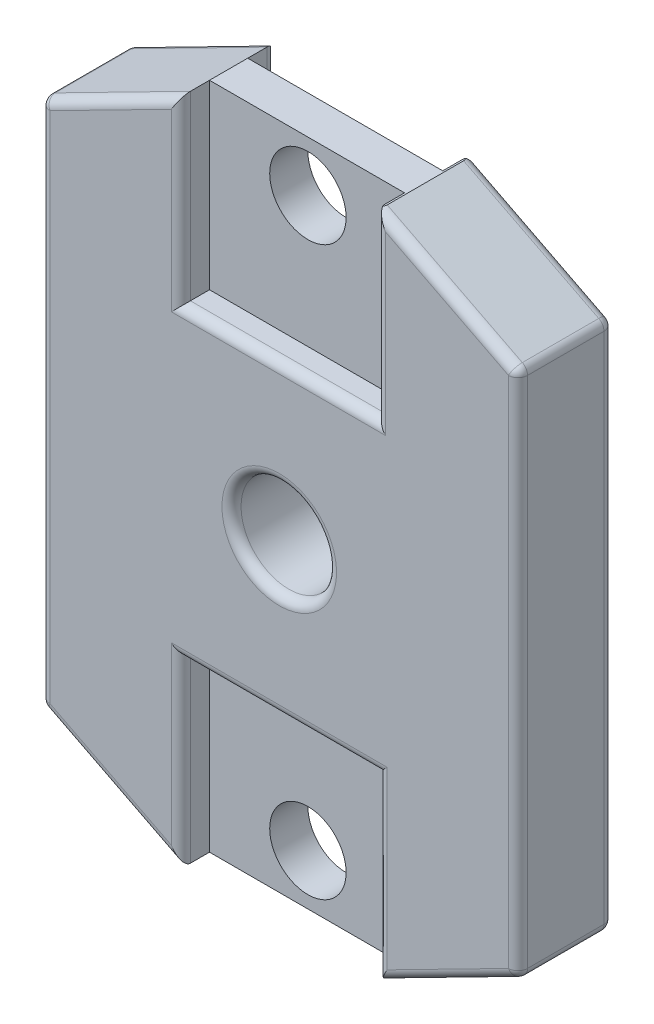
SolidWorks part; units mm, degrees
material "PC 高粘度"
ref_plane "前视基准面" through (0, 0, 0) normal (0, 0, 1) x (1, 0, 0)
ref_plane "上视基准面" through (0, 0, 0) normal (0, 1, 0) x (1, 0, 0)
ref_plane "右视基准面" through (0, 0, 0) normal (1, 0, 0) x (0, 0, -1)
sketch "草图1" plane through (0, 0, 0) normal (0, 0, 1) x (1, 0, 0)
  line L0 (0, 0) -> (5, 0)
  line L1 (0, 0) -> (0, 7)
  line L2 (0, 7) -> (5, 7)
  line L3 (5, 7) -> (5, 0)
  dimension "D1" = 5
extrude "凸台-拉伸1" add sketch "草图1" along normal blind 1
sketch "草图2" plane through (0, 0, 0) normal (0, 0, 1) x (1, 0, 0)
  line L0 (0, 7) -> (5, 0)
  line L1 (0, 0) -> (5, 0) construction
  line L2 (5, 0) -> (5, 7)
  line L3 (5, 7) -> (0, 0)
  circle A0 centre (2.5, 3.5) radius 0.9954
  circle A1 centre (2.5, 3.5) radius 0.7
  circle A2 centre (2.5, 3.5) radius 0.5
extrude "凸台-拉伸2" add sketch "草图2" against normal blind 0.25 contours A1 L3 A0 L0 | A1 L0 A0 L3 | A1 L3 A0 L0 | A1 L0 A0 L3 region at (2.5, 4.3024, 0) region at (1.767, 3.5, 0) region at (3.233, 3.5, 0) region at (2.5, 2.6976, 0)
sketch "草图4" plane through (0, 0, 0) normal (0, 0, -1) x (-1, 0, 0)
  circle A0 centre (-2.5, 3.5) radius 0.7
extrude "凸台-拉伸3" add sketch "草图4" along normal blind 0.35
sketch "草图5" plane through (0, 0, -0.35) normal (0, 0, -1) x (-1, 0, 0)
  circle A0 centre (-2.5, 3.5) radius 0.5
extrude "切除-拉伸1" cut sketch "草图5" against normal through all
sketch "草图7" plane through (0, 0, 0) normal (0, 0, 1) x (1, 0, 0)
  line L0 (3.5303, 0) -> (5, 0)
  line L1 (5, 0) -> (5, 7) construction
  line L2 (0, 0.75) -> (0, 0)
  line L3 (5, 6.25) -> (3.5303, 7)
  line L4 (5, 7) -> (0, 7) construction
  line L6 (5, 0.75) -> (3.5303, 0)
  line L7 (0, 0) -> (5, 0) construction
  line L9 (0, 7) -> (0, 0) construction
  line L11 (0, 0.75) -> (1.4697, 0)
  line L13 (1.4697, 7) -> (0, 6.25)
  line L14 (5, 6.25) -> (5, 7)
  line L15 (5, 7) -> (0, 7)
  line L16 (0, 7) -> (0, 6.25)
  line L17 (0, 0) -> (1.4697, 0)
  line L18 (5, 0) -> (5, 7)
extrude "切除-拉伸2" cut sketch "草图7" along normal through all contours L14 L15 L3 | L15 L16 L13 | L2 L17 L11 | L0 L18 L6 region at (4.5101, 0.25, 0) region at (0.4899, 6.75, 0) region at (4.5101, 6.75, 0) region at (0.4899, 0.25, 0)
sketch "草图8" plane through (0, 0, 0) normal (0, 0, 1) x (1, 0, 0)
  line L0 (1.4697, 7) -> (1.4697, 5.1)
  line L1 (1.4697, 5.1) -> (3.5121, 5.1)
  line L2 (3.5121, 5.1) -> (3.5121, 7)
  line L3 (3.5303, 7) -> (1.4697, 7) construction
  line L4 (3.5303, 0) -> (1.4697, 0)
  line L5 (1.4697, 0) -> (1.4697, 1.9)
  line L6 (1.4697, 1.9) -> (3.5303, 1.9)
  line L7 (3.5303, 1.9) -> (3.5303, 0)
  line L8 (3.5121, 7) -> (1.4697, 7)
  dimension "D1" = 1.9
  dimension "D2" = 1.9
extrude "切除-拉伸3" cut sketch "草图8" along normal blind 0.3
sketch "草图9" plane through (0, 0, 1) normal (0, 0, 1) x (1, 0, 0)
  line L0 (1.4697, 7) -> (1.4697, 5.1)
  line L1 (1.4697, 5.1) -> (3.5121, 5.1)
  line L2 (3.5121, 5.1) -> (3.5121, 7)
  line L3 (3.5121, 7) -> (1.4697, 7)
  line L4 (1.4697, 0) -> (3.5303, 0)
  line L5 (3.5303, 0) -> (3.5303, 1.9)
  line L6 (3.5303, 1.9) -> (1.4697, 1.9)
  line L7 (1.4697, 1.9) -> (1.4697, 0)
extrude "切除-拉伸4" cut sketch "草图9" against normal blind 0.3
sketch "草图10" plane through (0, 0, 0.3) normal (0, 0, -1) x (-1, 0, 0)
  line L0 (-2.5, 3.5) -> (-2.5, 6.47)
  line L1 (-2.5, 3.5) -> (-2.5, 0.53)
  dimension "D1" = 2.97
hole_wizard "Ø0.8 (0.8) 直径孔1" positions "草图11" profile "草图12" hole size "Ø0.8" standard "ISO" end condition up to next
sketch "草图11" plane through (0, 0, 0.3) normal (0, 0, -1) x (-1, 0, 0)
  point P0 (-2.5, 6.47)
  point P3 (-2.5, 0.53)
sketch "草图12" plane through (2.5, 6.47, 0.3) normal (1, 0, 0) x (0, 1, 0)
  line L0 (0, 0) -> (0, 0.4)
  line L1 (0, 0.4) -> (0.4, 0.4)
  line L2 (0.4, 0.4) -> (0.4, 0)
  line L5 (0.4, 0) -> (0, 0)
  line L11 (0, -6.35) -> (0, 107.95) construction
  dimension "通孔孔直径" = 0.8
  dimension "通孔孔深度" = 0.4
fillet "圆角1" radius 0.1 30 edges at (0.7348, 6.625, 1) (1.4697, 6.05, 1) (2.4909, 5.1, 1) (3.5121, 6.05, 1) (4.2652, 6.625, 1) (4.2652, 0.375, 1) (3.5303, 0.95, 1) (2.5, 1.9, 1) (1.4697, 0.95, 1) (0.7348, 0.375, 1) (2, 3.5, 1) (4.2652, 6.625, 0) (3.5121, 6.05, 0) (2.4909, 5.1, 0) (1.4697, 6.05, 0) (0.7348, 6.625, 0) (0.7348, 0.375, 0) (1.4697, 0.95, 0) (2.5, 1.9, 0) (3.5303, 0.95, 0) (4.2652, 0.375, 0) (1.5046, 3.5, 0) (0, 0.75, 0.5) (0, 3.5, 0) (0, 6.25, 0.5) (0, 3.5, 1) (5, 3.5, 1) (5, 6.25, 0.5) (5, 3.5, 0) (5, 0.75, 0.5)
fillet "圆角3" radius 0.05 2 edges at (3.2, 3.5, -0.25) (2, 3.5, -0.35)
